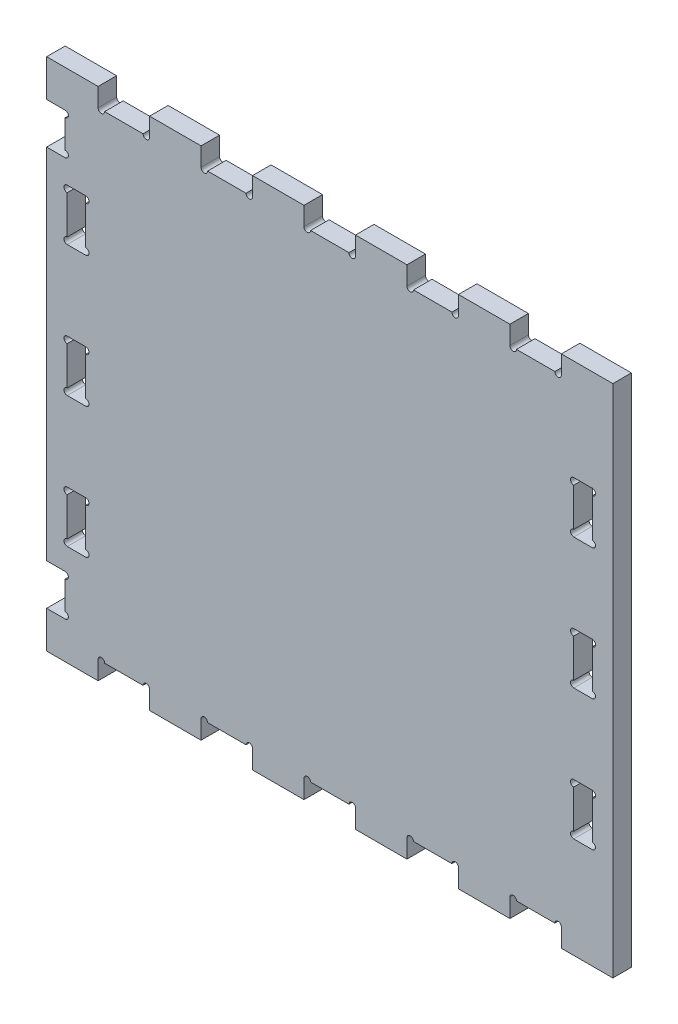
SolidWorks part; units mm, degrees
ref_plane "Piano frontale" through (0, 0, 0) normal (0, 0, 1) x (1, 0, 0)
ref_plane "Piano superiore" through (0, 0, 0) normal (0, 1, 0) x (1, 0, 0)
ref_plane "Piano destro" through (0, 0, 0) normal (1, 0, 0) x (0, 0, -1)
sketch "Schizzo2" plane through (0, 0, 0) normal (0, 0, 1) x (1, 0, 0)
  line L0 (-275, -250) -> (-275, -214)
  line L1 (-275, 250) -> (-225, 250)
  line L2 (-225, 250) -> (-225, 232)
  line L3 (-218.65, 232) -> (-181.35, 232)
  line L4 (-175, 232) -> (-175, 250)
  line L5 (-175, 250) -> (-125, 250)
  line L6 (-125, 250) -> (-125, 232)
  line L7 (-118.65, 232) -> (-81.35, 232)
  line L8 (-75, 232) -> (-75, 250)
  line L9 (-75, 250) -> (-25, 250)
  line L10 (-25, 250) -> (-25, 232)
  line L11 (-18.65, 232) -> (18.65, 232)
  line L12 (25, 232) -> (25, 250)
  line L13 (25, 250) -> (75, 250)
  line L14 (75, 250) -> (75, 232)
  line L15 (81.35, 232) -> (118.65, 232)
  line L16 (125, 232) -> (125, 250)
  line L17 (125, 250) -> (175, 250)
  line L18 (175, 250) -> (175, 232)
  line L19 (181.35, 232) -> (218.65, 232)
  line L20 (225, 232) -> (225, 250)
  line L21 (225, 250) -> (275, 250)
  line L22 (275, 250) -> (275, -250)
  line L23 (0, 0) -> (0, 370.058) construction
  line L24 (-255, 152) -> (-237, 152)
  line L25 (-255, 145.65) -> (-255, 108.35)
  line L26 (-255, 102) -> (-237, 102)
  line L27 (-237, 145.65) -> (-237, 108.35)
  line L28 (-275, 0) -> (275, 0) construction
  line L29 (237, 145.65) -> (237, 108.35)
  line L30 (255, 102) -> (237, 102)
  line L31 (255, 145.65) -> (255, 108.35)
  line L32 (255, 152) -> (237, 152)
  line L33 (255, -152) -> (237, -152)
  line L34 (255, -145.65) -> (255, -108.35)
  line L35 (255, -102) -> (237, -102)
  line L36 (237, -145.65) -> (237, -108.35)
  line L37 (-237, -145.65) -> (-237, -108.35)
  line L38 (-255, -102) -> (-237, -102)
  line L39 (-255, -145.65) -> (-255, -108.35)
  line L40 (-255, -152) -> (-237, -152)
  line L41 (225, -250) -> (275, -250)
  line L42 (225, -232) -> (225, -250)
  line L43 (181.35, -232) -> (218.65, -232)
  line L44 (175, -250) -> (175, -232)
  line L45 (125, -250) -> (175, -250)
  line L46 (125, -232) -> (125, -250)
  line L47 (81.35, -232) -> (118.65, -232)
  line L48 (75, -250) -> (75, -232)
  line L49 (25, -250) -> (75, -250)
  line L50 (25, -232) -> (25, -250)
  line L51 (-18.65, -232) -> (18.65, -232)
  line L52 (-25, -250) -> (-25, -232)
  line L53 (-75, -250) -> (-25, -250)
  line L54 (-75, -232) -> (-75, -250)
  line L55 (-118.65, -232) -> (-81.35, -232)
  line L56 (-125, -250) -> (-125, -232)
  line L57 (-175, -250) -> (-125, -250)
  line L58 (-175, -232) -> (-175, -250)
  line L59 (-218.65, -232) -> (-181.35, -232)
  line L60 (-225, -250) -> (-225, -232)
  line L61 (-275, -250) -> (-225, -250)
  line L62 (-255, 25) -> (-237, 25)
  line L63 (-237, -18.65) -> (-237, 18.65)
  line L64 (-255, -25) -> (-237, -25)
  line L65 (-255, -18.65) -> (-255, 18.65)
  line L66 (255, -18.65) -> (255, 18.65)
  line L67 (255, -25) -> (237, -25)
  line L68 (237, -18.65) -> (237, 18.65)
  line L69 (255, 25) -> (237, 25)
  line L70 (-275, 214) -> (-275, 250)
  line L71 (-275, 214) -> (-257, 214)
  line L72 (-275, -174) -> (-257, -174)
  line L73 (-275, 174) -> (-257, 174)
  line L74 (-257, 207.65) -> (-257, 180.35)
  line L75 (-257, -207.65) -> (-257, -180.35)
  line L76 (-275, -214) -> (-257, -214)
  line L77 (-275, -174) -> (-275, 174)
  line L78 (-257, 194) -> (-311.4817, 194) construction
  arc A0 (-255, 145.65) -> (-255, 152) centre (-255, 148.825) cw
  arc A1 (-255, 108.35) -> (-255, 102) centre (-255, 105.175) ccw
  arc A2 (-237, 108.35) -> (-237, 102) centre (-237, 105.175) cw
  arc A3 (-237, 145.65) -> (-237, 152) centre (-237, 148.825) ccw
  arc A4 (237, 145.65) -> (237, 152) centre (237, 148.825) cw
  arc A5 (237, 108.35) -> (237, 102) centre (237, 105.175) ccw
  arc A6 (255, 108.35) -> (255, 102) centre (255, 105.175) cw
  arc A7 (255, 145.65) -> (255, 152) centre (255, 148.825) ccw
  arc A8 (255, -145.65) -> (255, -152) centre (255, -148.825) cw
  arc A9 (255, -108.35) -> (255, -102) centre (255, -105.175) ccw
  arc A10 (237, -108.35) -> (237, -102) centre (237, -105.175) cw
  arc A11 (237, -145.65) -> (237, -152) centre (237, -148.825) ccw
  arc A12 (-237, -145.65) -> (-237, -152) centre (-237, -148.825) cw
  arc A13 (-237, -108.35) -> (-237, -102) centre (-237, -105.175) ccw
  arc A14 (-255, -108.35) -> (-255, -102) centre (-255, -105.175) cw
  arc A15 (-255, -145.65) -> (-255, -152) centre (-255, -148.825) ccw
  arc A16 (-255, 18.65) -> (-255, 25) centre (-255, 21.825) cw
  arc A17 (-237, 18.65) -> (-237, 25) centre (-237, 21.825) ccw
  arc A18 (-255, -18.65) -> (-255, -25) centre (-255, -21.825) ccw
  arc A19 (-237, -18.65) -> (-237, -25) centre (-237, -21.825) cw
  arc A20 (237, -18.65) -> (237, -25) centre (237, -21.825) ccw
  arc A21 (255, -18.65) -> (255, -25) centre (255, -21.825) cw
  arc A22 (237, 18.65) -> (237, 25) centre (237, 21.825) cw
  arc A23 (255, 18.65) -> (255, 25) centre (255, 21.825) ccw
  arc A24 (225, 232) -> (218.65, 232) centre (221.825, 232) cw
  arc A25 (175, 232) -> (181.35, 232) centre (178.175, 232) ccw
  arc A26 (125, 232) -> (118.65, 232) centre (121.825, 232) cw
  arc A27 (75, 232) -> (81.35, 232) centre (78.175, 232) ccw
  arc A28 (25, 232) -> (18.65, 232) centre (21.825, 232) cw
  arc A29 (-25, 232) -> (-18.65, 232) centre (-21.825, 232) ccw
  arc A30 (-75, 232) -> (-81.35, 232) centre (-78.175, 232) cw
  arc A31 (-125, 232) -> (-118.65, 232) centre (-121.825, 232) ccw
  arc A32 (-175, 232) -> (-181.35, 232) centre (-178.175, 232) cw
  arc A33 (-225, 232) -> (-218.65, 232) centre (-221.825, 232) ccw
  arc A34 (-175, -232) -> (-181.35, -232) centre (-178.175, -232) ccw
  arc A35 (-225, -232) -> (-218.65, -232) centre (-221.825, -232) cw
  arc A36 (-75, -232) -> (-81.35, -232) centre (-78.175, -232) ccw
  arc A37 (-25, -232) -> (-18.65, -232) centre (-21.825, -232) cw
  arc A38 (25, -232) -> (18.65, -232) centre (21.825, -232) ccw
  arc A39 (75, -232) -> (81.35, -232) centre (78.175, -232) cw
  arc A40 (125, -232) -> (118.65, -232) centre (121.825, -232) ccw
  arc A41 (175, -232) -> (181.35, -232) centre (178.175, -232) cw
  arc A42 (225, -232) -> (218.65, -232) centre (221.825, -232) ccw
  arc A43 (-125, -232) -> (-118.65, -232) centre (-121.825, -232) cw
  arc A44 (-257, 174) -> (-257, 180.35) centre (-257, 177.175) ccw
  arc A45 (-257, 214) -> (-257, 207.65) centre (-257, 210.825) cw
  arc A46 (-257, -174) -> (-257, -180.35) centre (-257, -177.175) cw
  arc A47 (-257, -214) -> (-257, -207.65) centre (-257, -210.825) ccw
  point P31 (-258.175, 148.825)
  point P101 (-246, 25)
  point P127 (221.825, 228.825)
  point P129 (-121.825, -232)
  dimension "D20" = 3.175
  dimension "D26" = 3.175
  dimension "D27" = 3.175
  dimension "D2" = 50
  dimension "D3" = 50
  dimension "D4" = 18
  dimension "D5" = 18
  dimension "D8" = 2
  dimension "D9" = 3.175
  dimension "D10" = 50
  dimension "D11" = 18
  dimension "D12" = 20
  dimension "D13" = 80
  dimension "D14" = 250
  dimension "D15" = 0
  dimension "D16" = 275
  dimension "D18" = 25
  dimension "D19" = 3.175
  dimension "D23" = 18
  dimension "D24" = 18
  dimension "D25" = 40
  dimension "D6" = 4
  dimension "D7" = 2
  dimension "D17" = 2
  dimension "D21" = 5
  dimension "D22" = 2
extrude "Estrusione-Estrusione1" add sketch "Schizzo2" along normal blind 18 contours L1 L2 A33 L3 A32 L4 L5 L6 A31 L7 A30 L8 L9 L10 A29 L11 A28 L12 L13 L14 A27 L15 A26 L16 L17 L18 A25 L19 A24 L20 L21 L22 L41 L42 A42 L43 A41 L44 L45 L46 A40 L47 A39 L48 L49 L50 A38 L51 A37 L52 L53 L54 A36 L55 A43 L56 L57 L58 A34 L59 A35 L60 L61 L0 L76 A47 L75 A46 L72 L77 L73 A44 L74 A45 L71 L70
extrude "Taglio-Estrusione1" cut sketch "Schizzo2<4>" along normal blind 115 contours L29 A5 L30 A6 L31 A7 L32 A4
sketch "Schizzo2<4>" plane through (0, 0, 0) normal (0, 0, 1) x (1, 0, 0) same geometry as "Schizzo2"
extrude "Taglio-Estrusione2" cut sketch "Schizzo2<5>" along normal blind 258 contours L68 A22 L69 A23 L66 A21 L67 A20
sketch "Schizzo2<5>" plane through (0, 0, 0) normal (0, 0, 1) x (1, 0, 0) same geometry as "Schizzo2"
extrude "Taglio-Estrusione3" cut sketch "Schizzo2<7>" along normal blind 723 contours L36 A10 L35 A9 L34 A8 L33 A11
sketch "Schizzo2<7>" plane through (0, 0, 0) normal (0, 0, 1) x (1, 0, 0) same geometry as "Schizzo2"
extrude "Taglio-Estrusione4" cut sketch "Schizzo2<8>" along normal blind 160 contours L25 A1 L26 A2 L27 A3 L24 A0
sketch "Schizzo2<8>" plane through (0, 0, 0) normal (0, 0, 1) x (1, 0, 0) same geometry as "Schizzo2"
extrude "Taglio-Estrusione5" cut sketch "Schizzo2<9>" along normal blind 190 contours L65 A16 L62 A17 L63 A19 L64 A18
sketch "Schizzo2<9>" plane through (0, 0, 0) normal (0, 0, 1) x (1, 0, 0) same geometry as "Schizzo2"
extrude "Taglio-Estrusione6" cut sketch "Schizzo2<10>" along normal blind 231 contours L39 A14 L38 A13 L37 A12 L40 A15
sketch "Schizzo2<10>" plane through (0, 0, 0) normal (0, 0, 1) x (1, 0, 0) same geometry as "Schizzo2"
